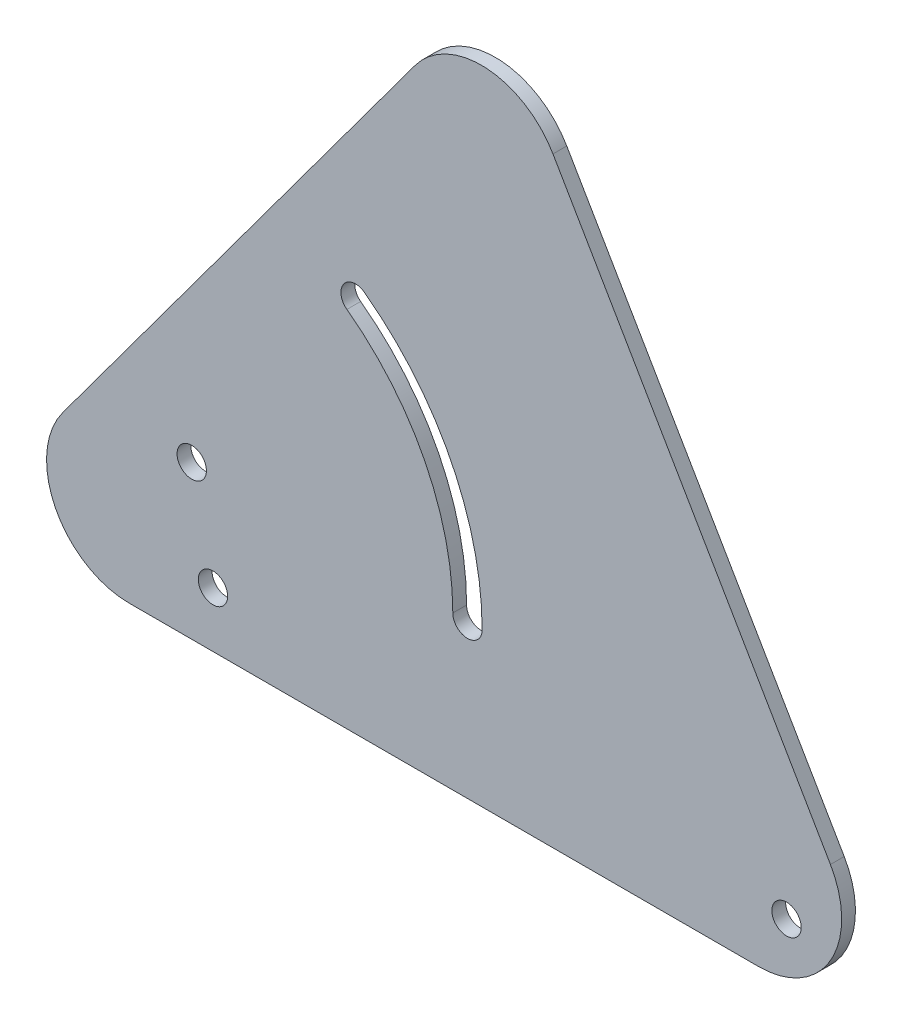
SolidWorks part; units mm, degrees
ref_plane "Front Plane" through (0, 0, 0) normal (0, 0, 1) x (1, 0, 0)
ref_plane "Top Plane" through (0, 0, 0) normal (0, 1, 0) x (1, 0, 0)
ref_plane "Right Plane" through (0, 0, 0) normal (1, 0, 0) x (0, 0, -1)
sketch "Sketch1" plane through (0, 0, 0) normal (0, 0, 1) x (1, 0, 0)
  line L3 (37.7646, 0) -> (182.767, 0)
  line L4 (199.2305, 28.6343) -> (135.3355, 138.3905)
  line L5 (103.5513, 140.1279) -> (22.444, 30.3716)
  arc A0 (37.7646, 0) -> (22.444, 30.3716) centre (37.7646, 19.05) cw
  arc A1 (182.767, 0) -> (199.2305, 28.6343) centre (182.767, 19.05) ccw
  arc A2 (135.3355, 138.3905) -> (103.5513, 140.1279) centre (118.872, 128.8062) ccw
  point P7 (0, 0)
  point P11 (215.9, 0)
  point P14 (120.7641, 163.4205)
  dimension "D4" = 19.05
  dimension "D1" = 215.9
  dimension "D2" = 127
  dimension "D3" = 203.2
base flange "Base-Flange1" sketch "Sketch1" thickness 3.175 reverse thickness direction no parameters "D1"=0.7366
sketch "Sketch6" plane through (0, 0, 0) normal (0, 0, 1) x (1, 0, 0)
  line L0 (103.5513, 140.1279) -> (22.444, 30.3716) construction
  line L1 (37.7646, 0) -> (182.767, 0) construction
  circle A0 centre (52.1462, 35.306) radius 3.3782
  arc A1 (89.8849, 86.3749) -> (115.6462, 35.306) centre (52.1462, 35.306) cw construction
  arc A2 (119.0244, 35.306) -> (91.8927, 89.0918) centre (52.1462, 35.306) ccw
  arc A3 (112.268, 35.306) -> (87.8772, 83.658) centre (52.1462, 35.306) ccw
  arc A4 (112.268, 35.306) -> (119.0244, 35.306) centre (115.6462, 35.306) ccw
  arc A5 (91.8927, 89.0918) -> (87.8772, 83.658) centre (89.8849, 86.3749) ccw
  point P4 (108.8412, 63.9053)
  dimension "D1" = 3.3782
  dimension "D2" = 6.7564
  dimension "D7" = 63.5
  dimension "D3" = 20.955
  dimension "D4" = 35.306
  dimension "D5" = 20.955
  dimension "D6" = 35.306
extrude "Cut-Extrude1" cut sketch "Sketch6" against normal through all normal cut yes
sketch "Sketch7" plane through (0, 0, 0) normal (0, 0, 1) x (1, 0, 0)
  line L0 (37.7646, 0) -> (182.767, 0) construction
  circle A0 centre (57.037, 12.7) radius 3.3782
  circle A1 centre (189.117, 12.7) radius 3.3782
  arc A4 (182.767, 0) -> (199.2305, 28.6343) centre (182.767, 19.05) ccw construction
  point P12 (0, 0)
  dimension "D1" = 6.7564
  dimension "D2" = 6.35
  dimension "D3" = 132.08
  dimension "D4" = 12.7
extrude "Cut-Extrude2" cut sketch "Sketch7" against normal through all normal cut yes
sketch "Bend-Lines1" [suppressed] plane through (0, 0, 0) normal (0, 1, 0) x (1, 0, 0)
sketch "Bounding-Box1" [suppressed] plane through (0, 0, 0) normal (0, 1, 0) x (1, 0, 0)
sheet metal parameters "Sheet-Metal1" thickness 3.175 parameters "D1"=0.7366
flat pattern "Flat-Pattern1" [suppressed]
sketch "Bend-Lines2" plane through (0, 0, 0) normal (0, 1, 0) x (1, 0, 0)
sketch3d "Bounding-Box2" [suppressed]
  line L0 (-26.6382, -61.7322, 0) -> (-112.4423, -3.3566, 0) construction
  line L1 (23.1985, 11.521, 0) -> (-62.6055, 69.8966, 0) construction
  line L2 (-26.6382, -61.7322, 0) -> (23.1985, 11.521, 0) construction
  line L3 (-112.4423, -3.3566, 0) -> (-62.6055, 69.8966, 0) construction
sheet metal parameters "Sheet-Metal2" thickness 3.175 parameters "D1"=0.7366
flat pattern "Flat-Pattern1"
sketch "Bend-Lines2" plane through (0, 0, 0) normal (0, 1, 0) x (1, 0, 0)
sketch3d "Bounding-Box2" [suppressed]
  line L0 (26.6382, -61.7322, 0) -> (112.4423, -3.3566, 0) construction
  line L1 (-23.1985, 11.521, 0) -> (62.6055, 69.8966, 0) construction
  line L2 (26.6382, -61.7322, 0) -> (-23.1985, 11.521, 0) construction
  line L3 (112.4423, -3.3566, 0) -> (62.6055, 69.8966, 0) construction
sheet metal parameters "Sheet-Metal3" thickness 3.175 parameters "D1"=0.7366
flat pattern "Flat-Pattern1"
sketch "Bend-Lines2" plane through (0, 0, 0) normal (0, 1, 0) x (1, 0, 0)
sketch3d "Bounding-Box2" [suppressed]
  line L0 (84.0128, 137.9851, 0) -> (161.2763, -7.9202, 0) construction
  line L1 (-55.5028, 64.1052, 0) -> (21.7608, -81.8001, 0) construction
  line L2 (84.0128, 137.9851, 0) -> (-55.5028, 64.1052, 0) construction
  line L3 (161.2763, -7.9202, 0) -> (21.7608, -81.8001, 0) construction
